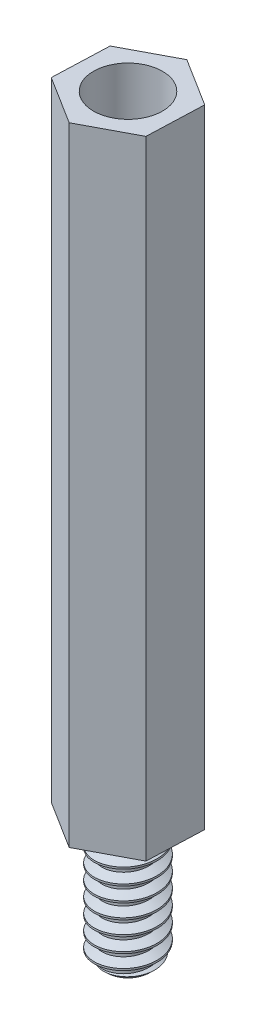
SolidWorks part; units mm, degrees
ref_plane "Front Plane" through (0, 0, 0) normal (0, 0, 1) x (1, 0, 0)
ref_plane "Top Plane" through (0, 0, 0) normal (0, 1, 0) x (1, 0, 0)
ref_plane "Right Plane" through (0, 0, 0) normal (1, 0, 0) x (0, 0, -1)
sketch "Sketch1" plane through (0, 0, 0) normal (0, 1, 0) x (1, 0, 0)
  line L1 (2.2983, -1.4426) -> (2.3985, 1.2691)
  line L2 (2.3985, 1.2691) -> (0.1002, 2.7117)
  line L3 (0.1002, 2.7117) -> (-2.2983, 1.4426)
  line L4 (-2.2983, 1.4426) -> (-2.3985, -1.2691)
  line L5 (-2.3985, -1.2691) -> (-0.1002, -2.7117)
  line L6 (-0.1002, -2.7117) -> (2.2983, -1.4426)
  circle A0 centre (0, 0) radius 2.35 construction
  dimension "D1" = 4.7
extrude "Boss-Extrude1" add sketch "Sketch1" along normal blind 30
hole_wizard "M4 Tapped Hole1" positions "Sketch2" profile "Sketch3" tap size "M4" standard "DIN"
sketch "Sketch2" plane through (0, 30, 0) normal (0, 1, 0) x (1, 0, 0)
  point P0 (0, 0)
sketch "Sketch3" plane through (0, 30, 0) normal (1, 0, 0) x (0, 0, 1)
  line L0 (0, 0) -> (0, 6.9914)
  line L1 (0, 6.9914) -> (1.65, 6)
  line L2 (1.65, 6) -> (1.65, 0)
  line L5 (1.65, 0) -> (0, 0)
  line L10 (0, 6.9914) -> (-1.65, 6) construction
  line L11 (0, -6.35) -> (0, 107.95) construction
  dimension "Tap Drill Dia." = 3.3
  dimension "Tap Drill Depth" = 6
  dimension "Drill Angle" = 118
cosmetic thread "Hole Thread1" parameters "D1"=6, "D2"=4
sketch "Sketch4" plane through (0, 0, 0) normal (0, -1, 0) x (1, 0, 0)
  circle A0 centre (0, 0) radius 1.5
  dimension "D1" = 3
extrude "Boss-Extrude2" add sketch "Sketch4" along normal blind 6
fillet "Fillet1" radius 0.5 1 edges at (0, -6, -1.5) conic radius 10
thread "Thread1" pitch 0.7 method cut profile "Thread Profile1" start angle 0, offset 0, length 0, pitch 0.7, diameter 3
ref_plane "Plane1" through (-1.5, 0, 0) normal (0, 0, 1) x (-1, 0, 0)
sketch "Thread Profile1" plane through (-1.5, 0, 0) normal (0, 0, 1) x (-1, 0, 0)
  line L0 (0, 0) -> (0, 0.7) construction
  line L11 (0, 0) -> (0, 0.6125)
  line L12 (0, 0.6125) -> (-0.3789, 0.3937)
  line L13 (-0.3789, 0.3937) -> (-0.3789, 0.2187)
  line L15 (-0.3789, 0.2187) -> (0, 0)
  line L17 (-0.3789, 0.3062) -> (0, 0.3062) construction
  point P2 (0, 0)
  dimension "Pitch" = 0.7
  dimension "Profile_Angle" = 60
  dimension "Profile_Land" = 0.175
  dimension "Profile_Height" = 0.3789
